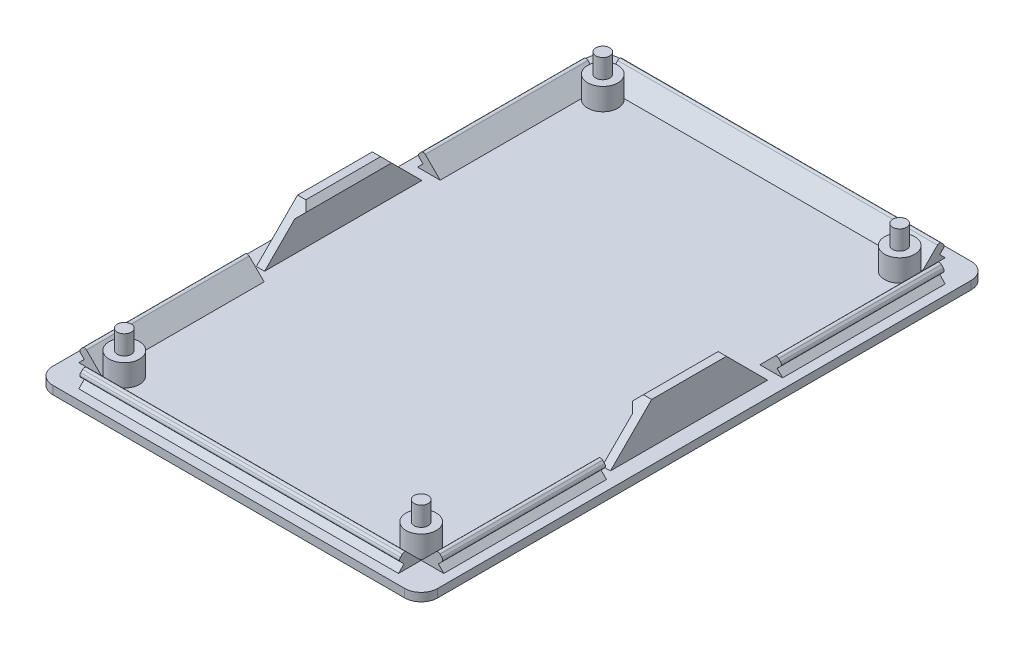
SolidWorks part; units mm, degrees
ref_plane "Front Plane" through (0, 0, 0) normal (0, 0, 1) x (1, 0, 0)
ref_plane "Top Plane" through (0, 0, 0) normal (0, 1, 0) x (1, 0, 0)
ref_plane "Right Plane" through (0, 0, 0) normal (1, 0, 0) x (0, 0, -1)
sketch "EDIT GLOBAL VARIABLE WITH PCB DIMENSIONS" plane through (0, 0, 0) normal (0, 1, 0) x (1, 0, 0)
  line L1 (-34.98, -51.49) -> (34.98, -51.49)
  line L2 (-34.98, -51.49) -> (-34.98, 51.49)
  line L3 (-34.98, 51.49) -> (34.98, 51.49)
  line L4 (34.98, -51.49) -> (34.98, 51.49)
  line L5 (-34.98, -51.49) -> (34.98, 51.49) construction
  line L6 (-34.98, 51.49) -> (34.98, -51.49) construction
  line L7 (-30.48, -46.99) -> (30.48, -46.99) construction
  line L8 (-30.48, -46.99) -> (-30.48, 46.99) construction
  line L9 (-30.48, 46.99) -> (30.48, 46.99) construction
  line L10 (30.48, -46.99) -> (30.48, 46.99) construction
  line L11 (-30.48, -46.99) -> (30.48, 46.99) construction
  line L12 (-30.48, 46.99) -> (30.48, -46.99) construction
  point P0 (0, 0)
  point P6 (0, 0)
  dimension "D3" = 4.5
  dimension "D4" = 4.5
  dimension "D2" = 93.98
  dimension "D17" = 60.96
extrude "Boss-Extrude1" add sketch "EDIT GLOBAL VARIABLE WITH PCB DIMENSIONS" along normal blind 1.5
fillet "Fillet1" radius 3 4 edges at (-34.98, 0.75, -51.49) (34.98, 0.75, -51.49) (34.98, 0.75, 51.49) (-34.98, 0.75, 51.49)
ref_plane "Plane1" through (-33.18, 0, 0) normal (-1, 0, 0) x (0, 0, 1)
ref_plane "Plane2" through (0, 0, 49.69) normal (0, 0, 1) x (1, 0, 0)
ref_plane "Plane3" through (33.18, 0, 0) normal (1, 0, 0) x (0, 0, -1)
ref_plane "Plane4" through (0, 0, -49.69) normal (0, 0, -1) x (-1, 0, 0)
ref_plane "Plane5" through (0, 0, -45.5687) normal (0, 0, -1) x (-1, 0, 0)
ref_plane "Plane6" through (-29.0587, 0, 0) normal (-1, 0, 0) x (0, 0, 1)
ref_plane "Plane7" through (0, 0, 45.5687) normal (0, 0, 1) x (1, 0, 0)
ref_plane "Plane8" through (29.0587, 0, 0) normal (1, 0, 0) x (0, 0, -1)
sketch "Sketch2" plane through (0, 0, 45.5687) normal (0, 0, 1) x (1, 0, 0)
  line L9 (33.18, 1.5) -> (29.0587, 1.5)
  line L11 (34.98, 1.5) -> (31.98, 1.5) construction
  line L12 (-31.98, 1.5) -> (31.98, 1.5) construction
  line L13 (29.0587, 1.5) -> (32.1193, 4.5607)
  line L14 (32.1193, 4.5607) -> (33.18, 3.5)
  line L15 (33.18, 3.5) -> (32.18, 2.5)
  line L16 (32.18, 2.5) -> (33.18, 1.5)
  line L17 (34.98, 1.5) -> (34.98, 0) construction
  line L18 (33.18, 3.5) -> (33.18, 1.5) construction
  dimension "D1" = 2
  dimension "D2" = 90
  dimension "D3" = 45
  dimension "D4" = 1.5
  dimension "D5" = 1.8
extrude "Boss-Extrude2" add sketch "Sketch2" against normal up to surface (91.1374 mm away) up to plane "Plane5"
sketch "Sketch3" plane through (0, 0, 45.5687) normal (0, 0, 1) x (1, 0, 0)
  line L9 (-33.18, 1.5) -> (-29.0587, 1.5)
  line L11 (-31.98, 1.5) -> (-34.98, 1.5) construction
  line L12 (-31.98, 1.5) -> (31.98, 1.5) construction
  line L13 (-29.0587, 1.5) -> (-32.1193, 4.5607)
  line L14 (-32.1193, 4.5607) -> (-33.18, 3.5)
  line L15 (-33.18, 3.5) -> (-32.18, 2.5)
  line L16 (-32.18, 2.5) -> (-33.18, 1.5)
  line L17 (-34.98, 0) -> (-34.98, 1.5) construction
  line L18 (-33.18, 3.5) -> (-33.18, 1.5) construction
  dimension "D1" = 45
  dimension "D2" = 90
  dimension "D3" = 1.5
  dimension "D4" = 2
  dimension "D5" = 1.8
extrude "Boss-Extrude3" add sketch "Sketch3" against normal up to surface (91.1374 mm away) up to plane "Plane5"
sketch "Sketch4" plane through (-29.0587, 0, 0) normal (-1, 0, 0) x (0, 0, 1)
  line L9 (-49.69, 1.5) -> (-45.5687, 1.5)
  line L12 (-48.49, 1.5) -> (-51.49, 1.5) construction
  line L13 (-48.49, 1.5) -> (48.49, 1.5) construction
  line L14 (-45.5687, 1.5) -> (-48.6293, 4.5607)
  line L15 (-48.6293, 4.5607) -> (-49.69, 3.5)
  line L16 (-49.69, 3.5) -> (-48.69, 2.5)
  line L17 (-48.69, 2.5) -> (-49.69, 1.5)
  line L18 (-51.49, 0) -> (-51.49, 1.5) construction
  dimension "D1" = 45
  dimension "D2" = 90
  dimension "D3" = 1.5
  dimension "D4" = 2
  dimension "D5" = 1.8
  dimension "D6" = 1.8
extrude "Boss-Extrude4" add sketch "Sketch4" against normal up to surface (58.1174 mm away) up to plane "Plane8"
sketch "Sketch5" plane through (-29.0587, 0, 0) normal (-1, 0, 0) x (0, 0, 1)
  line L0 (45.5687, 1.5) -> (49.69, 1.5)
  line L1 (-48.49, 1.5) -> (48.49, 1.5) construction
  line L2 (51.49, 1.5) -> (48.49, 1.5) construction
  line L3 (49.69, 1.5) -> (48.69, 2.5)
  line L4 (48.69, 2.5) -> (49.69, 3.5)
  line L5 (49.69, 3.5) -> (48.6293, 4.5607)
  line L6 (48.6293, 4.5607) -> (45.5687, 1.5)
  line L7 (51.49, 1.5) -> (51.49, 0) construction
  dimension "D1" = 45
  dimension "D2" = 90
  dimension "D3" = 1.5
  dimension "D4" = 90
  dimension "D5" = 1.8
  dimension "D6" = 1.8
  dimension "D7" = 2
extrude "Boss-Extrude5" add sketch "Sketch5" against normal up to surface (58.1174 mm away) up to plane "Plane8"
fillet "Fillet2" radius 0.5 8 edges at (0, 3.5, 49.69) (0, 4.5607, 48.6293) (-33.18, 3.5, 0) (-32.1193, 4.5607, 0) (0, 3.5, -49.69) (0, 4.5607, -48.6293) (33.18, 3.5, 0) (32.1193, 4.5607, 0)
sketch "Sketch7" plane through (0, 0, 0) normal (1, 0, 0) x (0, 0, -1)
  line L1 (45.5687, 1.5) -> (-45.5687, 1.5) construction
  line L2 (-16, 1.5) -> (-16, 4.3536)
  line L3 (45.5687, 4.3536) -> (-45.5687, 4.3536) construction
  line L4 (-16, 4.3536) -> (16, 4.3536)
  line L5 (16, 4.3536) -> (16, 1.5)
  line L6 (16, 1.5) -> (-16, 1.5)
  dimension "D1" = 32
  dimension "D2" = 16
extrude "Cut-Extrude1" cut sketch "Sketch7" against normal through all both and the other way through all
sketch "Sketch8" plane through (0, 1.5, 0) normal (0, 1, 0) x (1, 0, 0)
  line L0 (-34.98, 48.49) -> (-34.98, -48.49) construction
  line L1 (31.98, 51.49) -> (-31.98, 51.49) construction
  line L2 (34.98, -48.49) -> (34.98, 48.49) construction
  line L3 (-31.98, -51.49) -> (31.98, -51.49) construction
  circle A0 centre (-26.98, 43.49) radius 1.27
  circle A1 centre (26.98, 43.49) radius 1.27
  circle A2 centre (-26.98, -43.49) radius 1.27
  circle A3 centre (26.98, -43.49) radius 1.27
  dimension "D1" = 2.54
  dimension "D2" = 2.54
  dimension "D3" = 2.54
  dimension "D4" = 2.54
  dimension "D5" = 8
  dimension "D6" = 8
  dimension "D7" = 8
  dimension "D8" = 8
  dimension "D9" = 8
  dimension "D10" = 8
  dimension "D11" = 8
  dimension "D12" = 8
extrude "Boss-Extrude6" add sketch "Sketch8" along normal blind 7.5
sketch "Sketch10" plane through (0, 1.5, 0) normal (0, 1, 0) x (1, 0, 0)
  circle A0 centre (-26.98, 43.49) radius 2.75
  circle A1 centre (26.98, 43.49) radius 2.75
  circle A2 centre (26.98, -43.49) radius 2.75
  circle A3 centre (-26.98, -43.49) radius 2.75
  dimension "D1" = 5.5
  dimension "D2" = 5.5
  dimension "D3" = 5.5
  dimension "D4" = 5.5
extrude "Boss-Extrude7" add sketch "Sketch10" along normal blind 4
sketch "Sketch11" plane through (0, 0, 0) normal (0, 0, 1) x (1, 0, 0)
  line L0 (-32.18, 1.5) -> (-32.18, 9)
  line L1 (-31.98, 1.5) -> (-34.98, 1.5) construction
  line L2 (-32.18, 9) -> (-30.68, 9)
  line L3 (-30.68, 9) -> (-30.68, 1.5)
  line L4 (-33.18, 1.5) -> (-29.0587, 1.5) construction
  line L5 (-30.68, 1.5) -> (-32.18, 1.5)
  line L6 (-34.98, 0) -> (-34.98, 1.5) construction
  line L7 (32.18, 1.5) -> (32.18, 9)
  line L8 (34.98, 1.5) -> (31.98, 1.5) construction
  line L9 (30.68, 1.5) -> (30.68, 9)
  line L10 (30.68, 9) -> (32.18, 9)
  line L11 (32.18, 1.5) -> (30.68, 1.5)
  line L12 (34.98, 1.5) -> (34.98, 0) construction
  dimension "D1" = 7.5
  dimension "D2" = 1.5
  dimension "D3" = 2.8
  dimension "D4" = 7.5
  dimension "D5" = 1.5
  dimension "D6" = 2.8
extrude "Boss-Extrude8" add sketch "Sketch11" along normal mid plane 28.5865
sketch "Sketch12" plane through (0, 0, 0) normal (0, 0, 1) x (1, 0, 0)
  line L0 (30.68, 9) -> (30.68, 7)
  line L1 (30.68, 9) -> (30.68, 1.5) construction
  line L2 (30.68, 7) -> (29.68, 8)
  line L3 (29.68, 8) -> (30.68, 9)
  line L4 (-30.68, 9) -> (-30.68, 7)
  line L5 (-30.68, 1.5) -> (-30.68, 9) construction
  line L6 (-30.68, 7) -> (-29.68, 8)
  line L7 (-29.68, 8) -> (-30.68, 9)
extrude "Boss-Extrude9" add sketch "Sketch12" along normal mid plane 28.5865
chamfer "Chamfer1" distance 7.5 angle 45 4 edges at (31.43, 9, -14.2933) (31.43, 9, 14.2933) (-31.43, 9, -14.2933) (-31.43, 9, 14.2933)
equation "\"LENGTH\"= 3.7in  'longest of two dimensions of pcb"
equation "\"WIDTH\"= 2.4in   'shortest of two dimensions of pcb"
equation "\"D2@EDIT GLOBAL VARIABLE WITH PCB DIMENSIONS\" = \"LENGTH\""
equation "\"D17@EDIT GLOBAL VARIABLE WITH PCB DIMENSIONS\" = \"WIDTH\""
equation "\"HOLE_DIA\"= 0.1in  'mounting hole diameter"
equation "\"D1@Sketch8\"=\"HOLE_DIA\""
equation "\"D2@Sketch8\"=\"HOLE_DIA\""
equation "\"D3@Sketch8\"=\"HOLE_DIA\""
equation "\"D4@Sketch8\"=\"HOLE_DIA\""
equation "\"HOLE_DIST\"= 0.137795in  'distance to mount hole centerline from edge of PCB"
equation "\"D5@Sketch8\"=\"HOLE_DIST\"+4.5mm"
equation "\"D6@Sketch8\"=\"D5@Sketch8\""
equation "\"D7@Sketch8\"=\"D5@Sketch8\""
equation "\"D8@Sketch8\"=\"D5@Sketch8\""
equation "\"D9@Sketch8\"=\"D8@Sketch8\""
equation "\"D10@Sketch8\"=\"D7@Sketch8\""
equation "\"D11@Sketch8\"=\"D10@Sketch8\""
equation "\"D12@Sketch8\"=\"D5@Sketch8\""
equation "\"D2@Sketch10\"=\"D1@Sketch10\""
equation "\"D3@Sketch10\"=\"D1@Sketch10\""
equation "\"D4@Sketch10\"=\"D1@Sketch10\""
equation "\"D4@Sketch11\"=\"D1@Sketch11\""
equation "\"D5@Sketch11\"=\"D2@Sketch11\""
equation "\"D6@Sketch11\"=\"D3@Sketch11\""
equation "\"D2@Sketch7\"=\"D1@Sketch7\"/2"
equation "\"HEIGHT\"= 0.944882in  'height of the enclosure"
